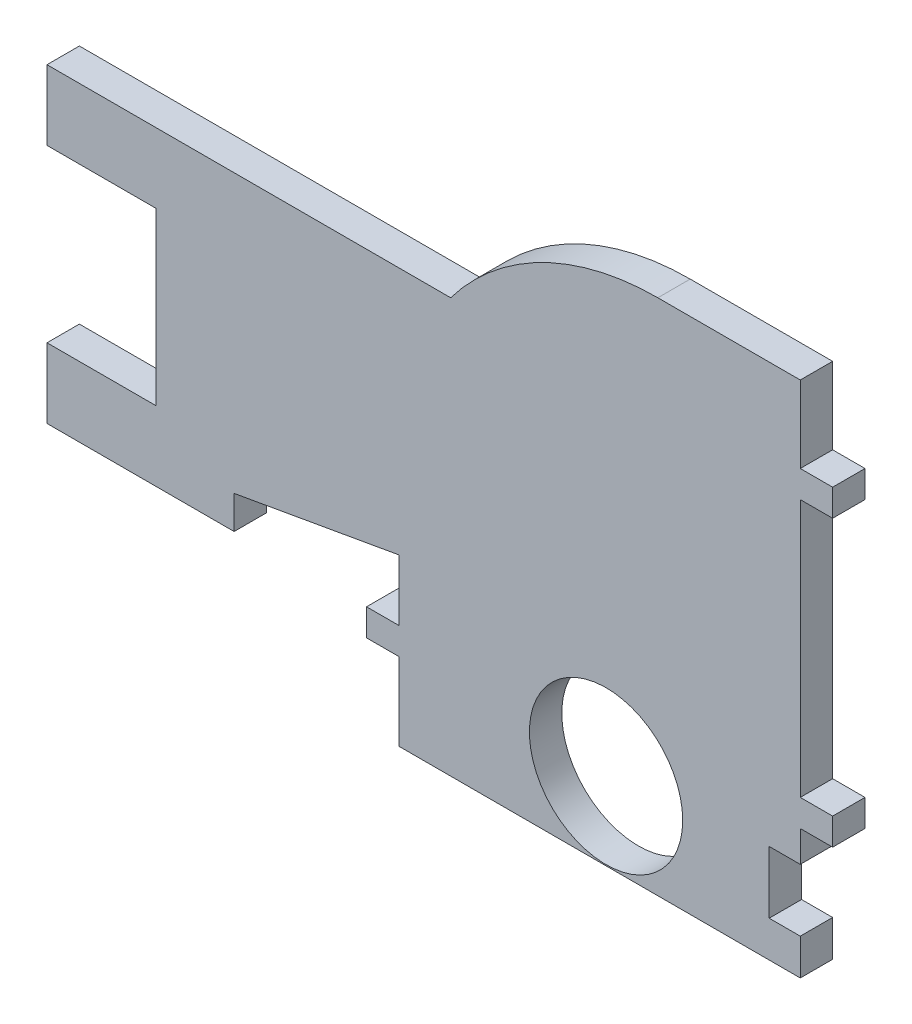
SolidWorks part; units mm, degrees
material "Balsa"
ref_plane "Front Plane" through (0, 0, 0) normal (0, 0, 1) x (1, 0, 0)
ref_plane "Top Plane" through (0, 0, 0) normal (0, 1, 0) x (1, 0, 0)
ref_plane "Right Plane" through (0, 0, 0) normal (1, 0, 0) x (0, 0, -1)
sketch "Sketch1" plane through (0, 0, 0) normal (0, 0, 1) x (1, 0, 0)
  line L0 (0, -1000.1535) -> (0, 48999.8465) construction
  line L1 (-7.62, 16.51) -> (-27.4189, 16.51)
  line L2 (-1000, 0) -> (49000, 0) construction
  line L3 (9.525, 16.51) -> (11.1125, 16.51)
  line L4 (2.54, 21.59) -> (9.525, 21.59)
  line L5 (-10.16, 8.89) -> (-10.16, -3.81)
  line L6 (-10.16, -3.81) -> (9.525, -3.81)
  line L7 (9.525, 21.59) -> (9.525, -3.81)
  line L8 (-11.7475, 0) -> (-10.16, 0)
  line L9 (-11.7475, 0) -> (-11.7475, 1.3208)
  line L10 (-11.7475, 1.3208) -> (-10.16, 1.3208)
  line L11 (-10.16, 0) -> (-10.16, 1.3208)
  line L12 (9.525, 2.54) -> (11.1125, 2.54)
  line L13 (9.525, 2.54) -> (9.525, 3.8608)
  line L14 (9.525, 3.8608) -> (11.1125, 3.8608)
  line L15 (11.1125, 2.54) -> (11.1125, 3.8608)
  line L16 (9.525, 16.51) -> (9.525, 17.8308)
  line L17 (9.525, 17.8308) -> (11.1125, 17.8308)
  line L18 (11.1125, 16.51) -> (11.1125, 17.8308)
  line L19 (-27.4189, 16.51) -> (-27.4189, 1.27)
  line L20 (-27.4189, 1.27) -> (-10.16, 4.318)
  line L21 (-27.4189, 13.081) -> (-22.0849, 13.081)
  line L22 (-22.0849, 13.081) -> (-22.0849, 4.699)
  line L23 (-22.0849, 4.699) -> (-27.4189, 4.699)
  line L24 (-27.4189, 1.27) -> (-18.2418, 1.27)
  line L25 (-18.2418, 1.27) -> (-18.2418, 2.8907)
  line L27 (9.525, 1.016) -> (8.001, 1.016)
  line L28 (9.525, 1.016) -> (9.525, -2.032)
  line L29 (9.525, -2.032) -> (8.001, -2.032)
  line L30 (8.001, 1.016) -> (8.001, -2.032)
  circle A0 centre (0, 0) radius 3.7592
  arc A3 (2.54, 21.59) -> (-10.16, 8.89) centre (2.54, 8.89) ccw
  dimension "D1" = 7.5184
  dimension "D4" = 3.81
  dimension "D3" = 3.7592
  dimension "D5" = 1.5875
  dimension "D9" = 12.7
  dimension "D10" = 1.5875
  dimension "D2" = 25.4
  dimension "D6" = 9.525
  dimension "D7" = 1.3208
  dimension "D8" = 19.685
  dimension "D11" = 2.54
  dimension "D12" = 1.3208
  dimension "D13" = 1.3208
  dimension "D14" = 1.5875
  dimension "D15" = 1.524
  dimension "D16" = 1.016
  dimension "D17" = 3.048
extrude "Boss-Extrude1" add sketch "Sketch1" along normal blind 1.5875 contours L4 A3 L5 L6 L7 A0 | L10 L9 L8 L5 | L3 L18 L17 L7 | L12 L15 L14 L7 | A3 L1 L19 L20 L5 | L24 L25 L20 region at (-17.5342, 9.9456, 0) region at (0.1298, 9.1228, 0) region at (10.3187, 17.1704, 0) region at (-10.9538, 0.6604, 0) region at (-21.3008, 1.8102, 0) region at (10.3187, 3.2004, 0)
move or copy body "Body-Move/Copy1" [suppressed] bodies to move or copy 101
